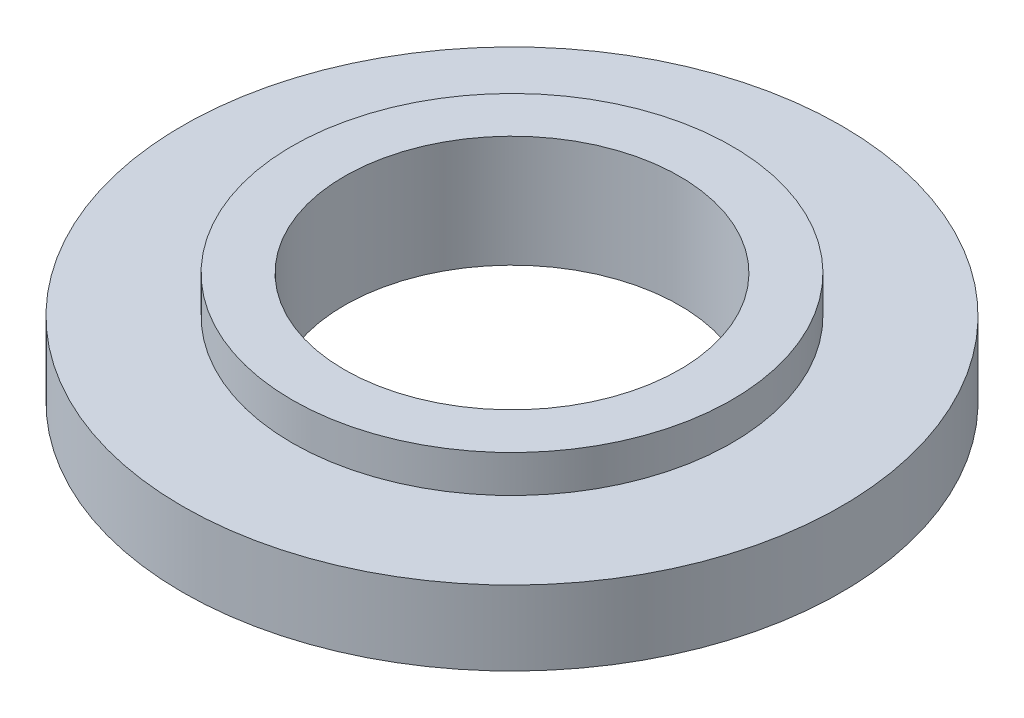
SolidWorks part; units mm, degrees
ref_plane "Front Plane" through (0, 0, 0) normal (0, 0, 1) x (1, 0, 0)
ref_plane "Top Plane" through (0, 0, 0) normal (0, 1, 0) x (1, 0, 0)
ref_plane "Right Plane" through (0, 0, 0) normal (1, 0, 0) x (0, 0, -1)
sketch "Sketch1" plane through (0, 0, 0) normal (0, 1, 0) x (1, 0, 0)
  circle A0 centre (0, 0) radius 22.479
  circle A1 centre (0, 0) radius 11.43
  dimension "D1" = 44.958
  dimension "D2" = 22.86
extrude "Boss-Extrude1" add sketch "Sketch1" along normal blind 5.08
sketch "Sketch2" plane through (0, 5.08, 0) normal (0, 1, 0) x (1, 0, 0)
  circle A0 centre (0, 0) radius 14.9987
  circle A1 centre (0, 0) radius 11.43
  dimension "D1" = 29.9974
extrude "Boss-Extrude2" add sketch "Sketch2" along normal blind 2.54
sketch "Sketch3" plane through (0, 5.08, 0) normal (0, 1, 0) x (1, 0, 0)
  circle A0 centre (-18.6235, -7.4138) radius 1.5875
  dimension "D1" = 3.175
sketch "Sketch4" plane through (0, 7.62, 0) normal (0, 1, 0) x (1, 0, 0)
